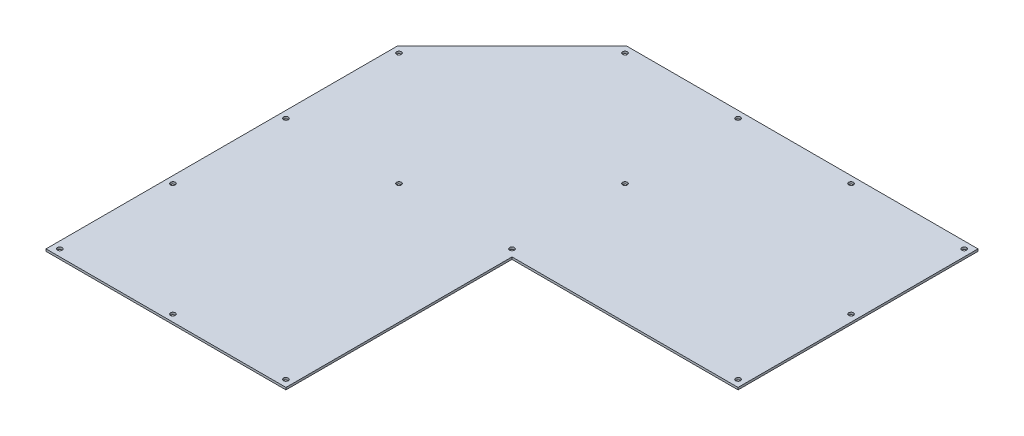
SolidWorks part; units mm, degrees
ref_plane "Front Plane" through (0, 0, 0) normal (0, 0, 1) x (1, 0, 0)
ref_plane "Top Plane" through (0, 0, 0) normal (0, 1, 0) x (1, 0, 0)
ref_plane "Right Plane" through (0, 0, 0) normal (1, 0, 0) x (0, 0, -1)
sketch "Sketch1" plane through (0, 0, 0) normal (0, 1, 0) x (1, 0, 0)
  line L0 (0, 0) -> (0, 256.54)
  line L1 (0, 256.54) -> (83.82, 340.36)
  line L2 (83.82, 340.36) -> (340.36, 340.36)
  line L3 (340.36, 340.36) -> (340.36, 165.1)
  line L4 (340.36, 165.1) -> (175.26, 165.1)
  line L5 (175.26, 165.1) -> (175.26, 0)
  line L6 (175.26, 0) -> (0, 0)
  dimension "D1" = 175.26
  dimension "D2" = 340.36
  dimension "D3" = 340.36
  dimension "D4" = 175.26
  dimension "D5" = 256.54
  dimension "D6" = 256.54
base flange "Base-Flange1" sketch "Sketch1" thickness 1.5875 reverse thickness direction no parameters "D1"=1.5875
hole_wizard "#29 (0.136) Diameter Hole1" positions "Sketch7" profile "Sketch6" hole size "#29" standard "ANSI Inch"
sketch "Sketch7" plane through (0, 0, 0) normal (0, 1, 0) x (1, 0, 0)
  line L0 (0, 256.54) -> (0, 0) construction
  line L1 (0, 0) -> (175.26, 0) construction
  line L2 (340.36, 165.1) -> (340.36, 340.36) construction
  line L3 (175.26, 165.1) -> (340.36, 165.1) construction
  point P0 (5.08, 5.08)
  point P22 (335.28, 170.18)
  point P33 (87.63, 5.08)
  point P35 (170.18, 5.08)
  point P37 (5.08, 87.63)
  point P39 (5.08, 170.18)
  point P41 (5.08, 252.73)
  point P43 (335.28, 252.73)
  point P45 (335.28, 335.28)
  point P48 (252.73, 335.28)
  point P50 (170.18, 335.28)
  point P52 (87.63, 335.28)
  point P53 (170.18, 170.18)
  point P56 (87.63, 170.18)
  point P58 (170.18, 252.73)
  dimension "D1" = 5.08
  dimension "D2" = 5.08
  dimension "D3" = 5.08
  dimension "D4" = 5.08
  dimension "D5" = 82.55
  dimension "D6" = 82.55
  dimension "D7" = 82.55
  dimension "D8" = 82.55
  dimension "D9" = 82.55
  dimension "D10" = 82.55
  dimension "D11" = 82.55
  dimension "D12" = 82.55
  dimension "D13" = 82.55
  dimension "D14" = 82.55
  dimension "D15" = 165.1
  dimension "D16" = 165.1
  dimension "D17" = 165.1
  dimension "D18" = 82.55
  dimension "D19" = 82.55
  dimension "D20" = 82.55
  dimension "D21" = 82.55
sketch "Sketch6" plane through (5.08, 0, -5.08) normal (1, 0, 0) x (0, 0, 1)
  line L0 (0, 0) -> (0, 7.3878)
  line L1 (0, 7.3878) -> (1.7272, 6.35)
  line L2 (1.7272, 6.35) -> (1.7272, 0)
  line L5 (1.7272, 0) -> (0, 0)
  line L10 (0, 7.3878) -> (-1.7272, 6.35) construction
  line L11 (0, -6.35) -> (0, 107.95) construction
  dimension "Hole Dia." = 3.4544
  dimension "Hole Depth" = 6.35
  dimension "Drill Angle" = 118
sketch "Bend-Lines1" plane through (0, 0, 0) normal (0, 1, 0) x (1, 0, 0)
sketch "Bounding-Box1" plane through (0, 0, 0) normal (0, 1, 0) x (1, 0, 0)
sheet metal parameters "Sheet-Metal1" thickness 1.5875 parameters "D1"=1.5875
flat pattern "Flat-Pattern1" [suppressed]
sketch "Bend-Lines2" plane through (0, 0, 0) normal (0, 1, 0) x (1, 0, 0)
sketch "Bounding-Box2" [suppressed] plane through (0, 0, 0) normal (0, 1, 0) x (1, 0, 0)
sheet metal parameters "Sheet-Metal2" thickness 1.5875 parameters "D1"=1.5875
flat pattern "Flat-Pattern1"
sketch "Bend-Lines2" plane through (0, 0, 0) normal (0, 1, 0) x (1, 0, 0)
sketch "Bounding-Box2" [suppressed] plane through (0, 0, 0) normal (0, 1, 0) x (1, 0, 0)
